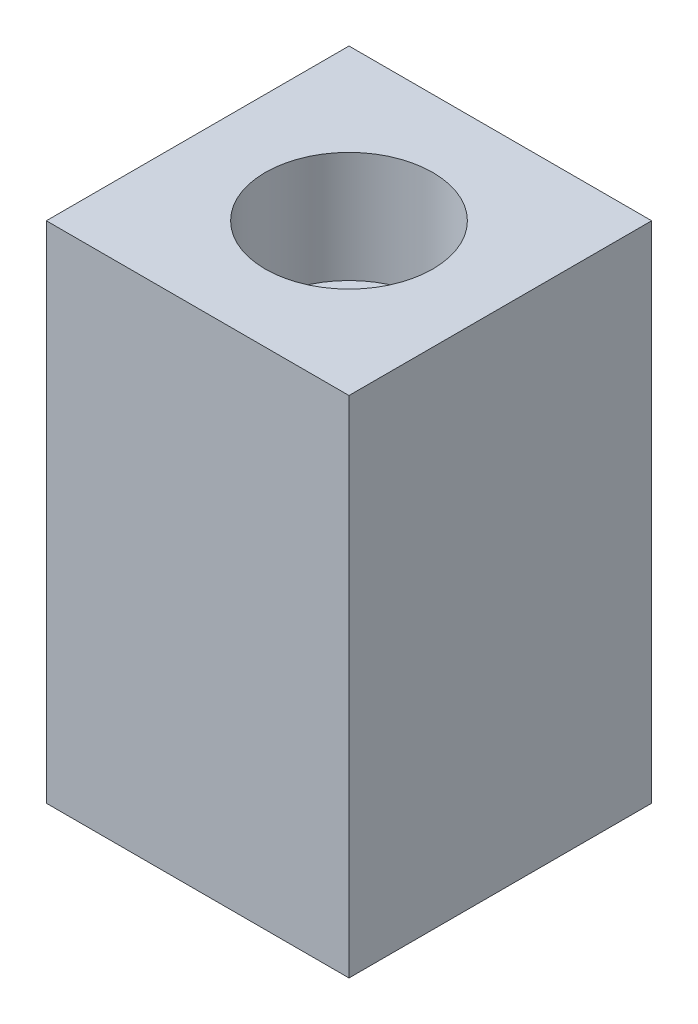
SolidWorks part; units mm, degrees
ref_plane "Ebene vorne" through (0, 0, 0) normal (0, 0, 1) x (1, 0, 0)
ref_plane "Ebene oben" through (0, 0, 0) normal (0, 1, 0) x (1, 0, 0)
ref_plane "Ebene rechts" through (0, 0, 0) normal (1, 0, 0) x (0, 0, -1)
sketch "Sketch3" plane through (0, 0, 0) normal (0, 1, 0) x (1, 0, 0)
  line L0 (0, 13.1643) -> (0, -11.9056) construction
  line L1 (-7.5, 7.5) -> (7.5, 7.5)
  line L2 (-7.5, 7.5) -> (-7.5, -7.5)
  line L3 (-7.5, -7.5) -> (7.5, -7.5)
  line L4 (7.5, 7.5) -> (7.5, -7.5)
  line L5 (-26.5385, 0) -> (29.5804, 0) construction
  dimension "D1" = 15
extrude "Boss-Extrude1" add sketch "Sketch3" along normal blind 25
sketch "Sketch4" plane through (0, 25, 0) normal (0, 1, 0) x (1, 0, 0)
  circle A0 centre (0, 0) radius 4.15
  circle A1 centre (0, 0) radius 3.15
  dimension "D1" = 8.3
  dimension "D2" = 6.3
extrude "Cut-Extrude1" cut sketch "Sketch4" against normal through all contours A1
extrude "Cut-Extrude2" cut sketch "Sketch4<3>" against normal blind 5.5 contours A0
sketch "Sketch4<3>" plane through (0, 25, 0) normal (0, 1, 0) x (1, 0, 0) same geometry as "Sketch4"
extrude "Cut-Extrude3" cut sketch "Sketch4<4>" along normal blind 5.5 from surface contours A0 starting at face at (0, 0, 3.15)
sketch "Sketch4<4>" plane through (0, 25, 0) normal (0, 1, 0) x (1, 0, 0) same geometry as "Sketch4"
